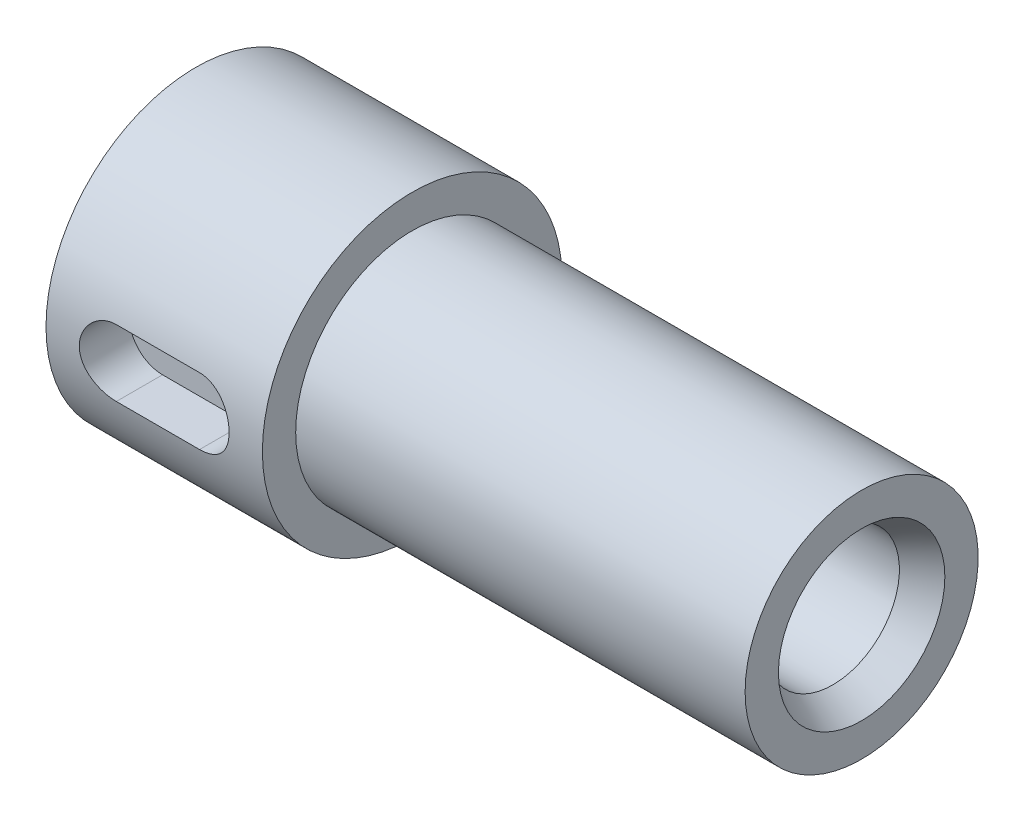
SolidWorks part; units mm, degrees
ref_plane "前视基准面" through (0, 0, 0) normal (0, 0, 1) x (1, 0, 0)
ref_plane "上视基准面" through (0, 0, 0) normal (0, 1, 0) x (1, 0, 0)
ref_plane "右视基准面" through (0, 0, 0) normal (1, 0, 0) x (0, 0, -1)
other "Configuration Table"
sketch "草图1" plane through (0, 0, 0) normal (0, 0, 1) x (1, 0, 0)
  line L0 (-23.3569, 0) -> (35.6421, 0) construction
  line L1 (0, 9) -> (13, 9)
  line L2 (13, 9) -> (13, 7)
  line L3 (13, 7) -> (40, 7)
  line L4 (40, 7) -> (40, 5)
  line L5 (38.2679, 4) -> (0.5774, 4)
  line L6 (0, 5) -> (0, 9)
  line L7 (40, 5) -> (38.2679, 4)
  line L8 (0.5774, 4) -> (0, 5)
  point P8 (40, 4)
  point P9 (0, 4)
  dimension "D1" = 40
  dimension "D2" = 13
  dimension "D3" = 4
  dimension "D4" = 9
  dimension "D5" = 7
  dimension "D6" = 1
  dimension "D7" = 60
  dimension "D8" = 1
  dimension "D9" = 30
revolve "旋转1" add sketch "草图1" angle 360 about L0
ref_plane "基准面1" through (0, 0, 9) normal (0, 0, 1) x (1, 0, 0)
sketch "草图2" plane through (0, 0, 9) normal (0, 0, 1) x (1, 0, 0)
  line L0 (4, 0) -> (9, 0) construction
  line L1 (4, 2) -> (9, 2)
  line L2 (4, -2) -> (9, -2)
  line L3 (0, 9) -> (0, -9) construction
  arc A0 (4, 2) -> (4, -2) centre (4, 0) ccw
  arc A1 (9, -2) -> (9, 2) centre (9, 0) ccw
  point P3 (6.5, 0)
  dimension "D2" = 2
  dimension "D1" = 5
  dimension "D3" = 4
extrude "切除-拉伸1" cut sketch "草图2" against normal blind 3
hole_wizard "M4 螺纹孔1" positions "草图4" profile "草图5" tap size "M4" standard "ISO" end condition up to next
sketch "草图4" plane through (0, 0, 6) normal (0, 0, 1) x (1, 0, 0)
  point P0 (9, 0)
sketch "草图5" plane through (9, 0, 6) normal (1, 0, 0) x (0, -1, 0)
  line L0 (0, 0) -> (0, 2)
  line L1 (0, 2) -> (1.65, 2)
  line L2 (1.65, 2) -> (1.65, 0.375)
  line L3 (1.65, 0.375) -> (2.025, 0)
  line L5 (2.025, 0) -> (0, 0)
  line L6 (-1.65, 0.375) -> (-2.025, 0) construction
  line L11 (0, -6.35) -> (0, 107.95) construction
  dimension "通孔螺纹孔钻头直径" = 3.3
  dimension "通孔螺纹孔钻头深度" = 2
  dimension "近端锥形沉头孔直径" = 4.05
  dimension "近端锥形沉头孔角度" = 90
cosmetic thread "孔螺蚊线1" parameters "D2"=4
ref_plane "基准面2" through (0, 0, -9) normal (0, 0, 1) x (1, 0, 0)
hole_wizard "M3 六角凹锥坑螺钉的锥形沉头孔1" positions "草图7" profile "草图8" countersink size "M3" standard "ISO" end condition up to next
sketch "草图7" plane through (0, 0, -9) normal (0, 0, 1) x (1, 0, 0)
  point P0 (4, 0)
sketch "草图8" plane through (4, 0, -9) normal (1, 0, 0) x (0, 1, 0)
  line L0 (0, 0) -> (0, 5)
  line L1 (0, 5) -> (1.8, 5)
  line L2 (1.8, 5) -> (1.8, 1.56)
  line L3 (1.8, 1.56) -> (3.36, 0)
  line L5 (3.36, 0) -> (0, 0)
  line L6 (-1.8, 1.56) -> (-3.36, 0) construction
  line L11 (0, -6.35) -> (0, 107.95) construction
  dimension "通孔孔直径" = 3.6
  dimension "通孔孔深度" = 5
  dimension "近端锥形沉头孔直径" = 6.72
  dimension "近端锥形沉头孔角度" = 90
